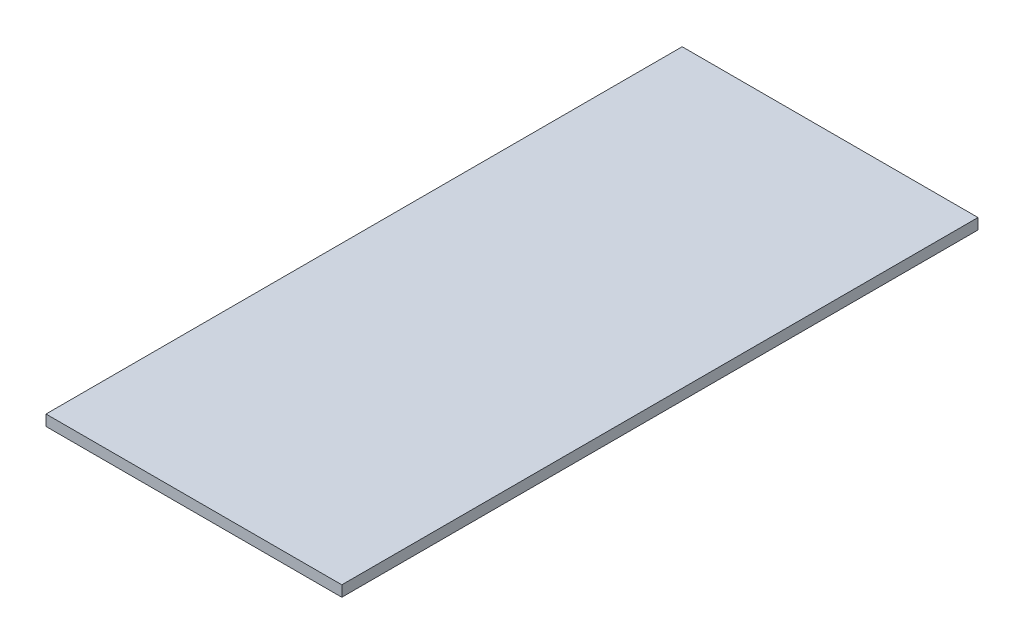
SolidWorks part; units mm, degrees
ref_plane "Alzado" through (0, 0, 0) normal (0, 0, 1) x (1, 0, 0)
ref_plane "Planta" through (0, 0, 0) normal (0, 1, 0) x (1, 0, 0)
ref_plane "Vista lateral" through (0, 0, 0) normal (1, 0, 0) x (0, 0, -1)
sketch "Croquis1" plane through (0, 0, 0) normal (0, 1, 0) x (1, 0, 0)
  line L1 (-46.5, 100) -> (46.5, 100)
  line L2 (-46.5, 100) -> (-46.5, -100)
  line L3 (-46.5, -100) -> (46.5, -100)
  line L4 (46.5, 100) -> (46.5, -100)
  line L5 (-46.5, 100) -> (46.5, -100) construction
  line L6 (-46.5, -100) -> (46.5, 100) construction
  point P0 (0, 0)
  dimension "D1" = 93
  dimension "D2" = 200
extrude "Saliente-Extruir1" add sketch "Croquis1" along normal blind 3.4
